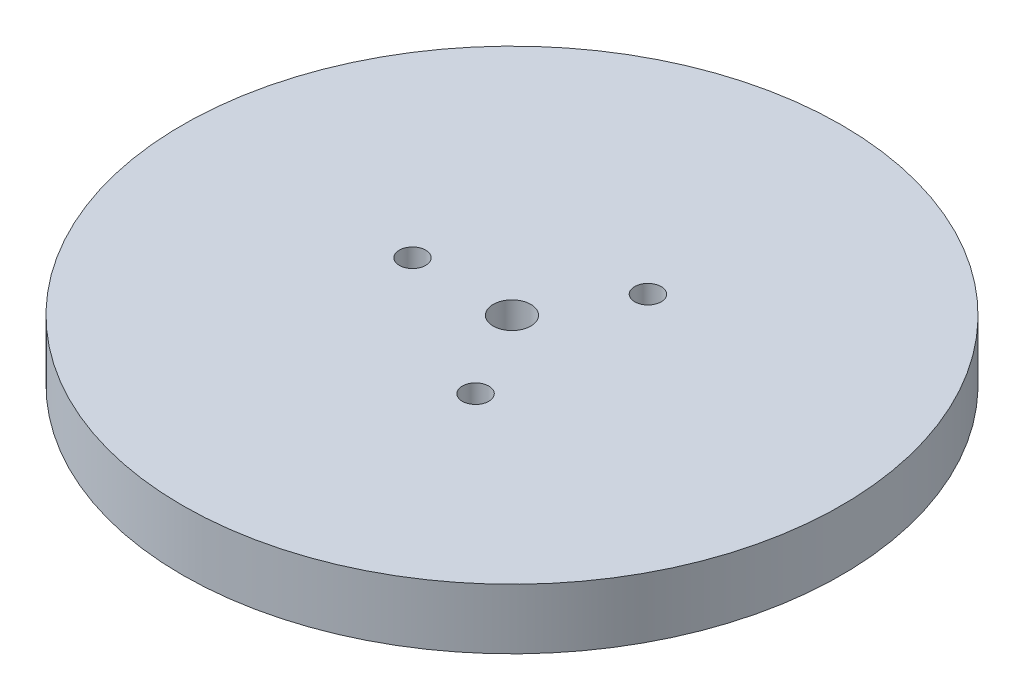
SolidWorks part; units mm, degrees
ref_plane "Front Plane" through (0, 0, 0) normal (0, 0, 1) x (1, 0, 0)
ref_plane "Top Plane" through (0, 0, 0) normal (0, 1, 0) x (1, 0, 0)
ref_plane "Right Plane" through (0, 0, 0) normal (1, 0, 0) x (0, 0, -1)
sketch "Sketch1" plane through (0, 0, 0) normal (0, 1, 0) x (1, 0, 0)
  circle A0 centre (0, 0) radius 87.5
  dimension "FLANGE_OD" = 175
extrude "Boss-Extrude1" add sketch "Sketch1" along normal blind 16
sketch "Sketch2" plane through (0, 0, 0) normal (0, 1, 0) x (1, 0, 0)
  circle A0 centre (0, 0) radius 5
  dimension "BORE_D" = 10
extrude "Cut-Extrude1" cut sketch "Sketch2" along normal through all
sketch "Sketch3" plane through (0, 16, 0) normal (0, 1, 0) x (1, 0, 0)
  circle A0 centre (0, 0) radius 26.4178 construction
  circle A1 centre (-26.4178, 0) radius 3.515
  dimension "BOLT_D" = 7.03
  dimension "BOLT_PCD" = 52.8357
extrude "Cut-Extrude2" cut sketch "Sketch3" against normal blind 13.9601
pattern_circular "CirPattern1" count 3 over 360 about axis through (0, 0, 0) along (0, 1, 0) of "Cut-Extrude2"
